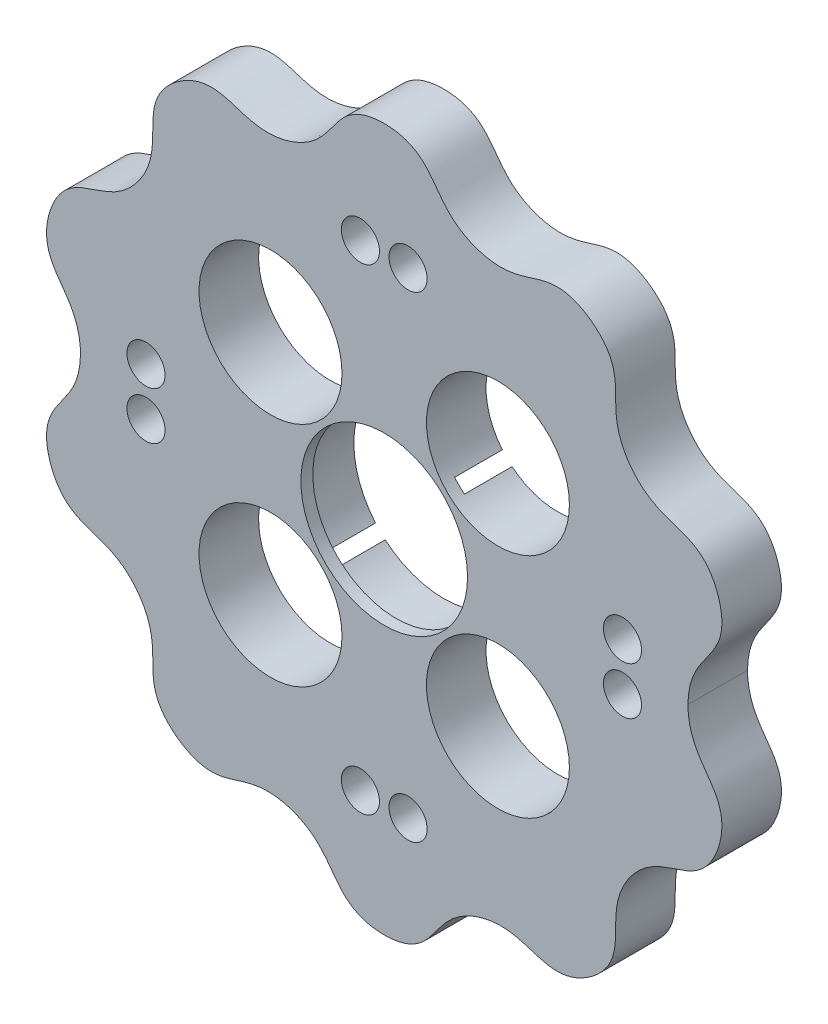
SolidWorks part; units mm, degrees
ref_plane "Front Plane" through (0, 0, 0) normal (0, 0, 1) x (1, 0, 0)
ref_plane "Top Plane" through (0, 0, 0) normal (0, 1, 0) x (1, 0, 0)
ref_plane "Right Plane" through (0, 0, 0) normal (1, 0, 0) x (0, 0, -1)
ref_plane "Plane1" through (0, 0, 4) normal (0, 0, 1) x (1, 0, 0)
sketch "Sketch3" plane through (0, 0, 4) normal (0, 0, 1) x (1, 0, 0)
  circle A0 centre (2, 0) radius 7.5
  spline S0 degree 5 poles (-23.5, 0) (-23.5, -0.6619) (-23.5985, -1.4561) (-23.8874, -2.4734) (-24.5265, -3.4803) (-25.3239, -4.5428) (-25.7599, -5.1922) (-26.203, -6.107) (-26.3992, -6.9747) (-26.3685, -8.1757) (-26.0322, -9.4106) (-25.4671, -10.5179) (-24.8895, -11.2256) (-23.9802, -11.9083) (-23.1576, -12.2723) (-21.7572, -12.687) (-20.1242, -13.2676) (-18.7699, -14.5833) (-17.7259, -16.1905) (-17.3933, -18.0022) (-17.4393, -19.3418) (-17.4288, -20.3924) (-17.2271, -21.518) (-16.8759, -22.3353) (-16.145, -23.2889) (-15.1471, -24.0902) (-14.0391, -24.6539) (-13.1558, -24.8869) (-12.0189, -24.9048) (-11.1394, -24.7158) (-9.7628, -24.2281) (-8.1004, -23.738) (-6.2314, -24.0063) (-4.442, -24.693) (-3.1081, -25.9632) (-2.3579, -27.074) (-1.7319, -27.9177) (-0.9071, -28.7098) (-0.1425, -29.1646) (1.0093, -29.5065) (2.2876, -29.5682) (3.5153, -29.373) (4.3668, -29.0423) (5.2971, -28.3885) (5.8976, -27.7187) (6.7246, -26.515) (7.7814, -25.1413) (9.4513, -24.2598) (11.3025, -23.7636) (13.1282, -24.0071) (14.3881, -24.4648) (15.3905, -24.7795) (16.5233, -24.9355) (17.4092, -24.854) (18.5419, -24.4536) (19.6124, -23.7522) (20.4909, -22.8726) (20.9855, -22.1045) (21.3538, -21.0288) (21.4458, -20.1339) (21.4074, -18.674) (21.455, -16.9415) (22.2878, -15.2469) (23.4937, -13.7573) (25.1139, -12.8812) (26.4022, -12.5109) (27.3981, -12.1763) (28.4063, -11.6367) (29.0751, -11.05) (29.7562, -10.0602) (30.2099, -8.8636) (30.4037, -7.6356) (30.3523, -6.7236) (30.018, -5.6368) (29.5664, -4.8587) (28.6772, -3.7002) (27.9235, -2.6005) (27.5985, -1.4561) (27.5, -0.6619) (27.5, 0) knots 0.5 0.5 0.5 0.5 0.5 0.5 0.516667 0.52 0.526667 0.53 0.533333 0.536667 0.546667 0.55 0.56 0.563333 0.566667 0.57 0.58 0.583333 0.6 0.61 0.616667 0.626667 0.63 0.633333 0.636667 0.646667 0.65 0.66 0.663333 0.666667 0.67 0.68 0.683333 0.7 0.71 0.716667 0.726667 0.73 0.733333 0.736667 0.746667 0.75 0.76 0.763333 0.766667 0.77 0.78 0.783333 0.8 0.81 0.816667 0.826667 0.83 0.833333 0.836667 0.846667 0.85 0.86 0.863333 0.866667 0.87 0.88 0.883333 0.9 0.91 0.916667 0.926667 0.93 0.933333 0.936667 0.946667 0.95 0.96 0.963333 0.966667 0.97 0.98 0.983333 1 1 1 1 1 1 weights 1 1 1 1 1 1 1 1 1 1 1 1 1 1 1 1 1 1 1 1 1 1 1 1 1 1 1 1 1 1 1 1 1 1 1 1 1 1 1 1 1 1 1 1 1 1 1 1 1 1 1 1 1 1 1 1 1 1 1 1 1 1 1 1 1 1 1 1 1 1 1 1 1 1 1 1 1 1 1 1
  spline S1 degree 5 poles (27.5, 0) (27.5, 0.6619) (27.5985, 1.4561) (27.8874, 2.4734) (28.5265, 3.4803) (29.3239, 4.5428) (29.7599, 5.1922) (30.203, 6.107) (30.3992, 6.9747) (30.3685, 8.1757) (30.0322, 9.4106) (29.4671, 10.5179) (28.8895, 11.2256) (27.9802, 11.9083) (27.1576, 12.2723) (25.7572, 12.687) (24.1242, 13.2676) (22.7699, 14.5833) (21.7259, 16.1905) (21.3933, 18.0022) (21.4393, 19.3418) (21.4288, 20.3924) (21.2271, 21.518) (20.8759, 22.3353) (20.145, 23.2889) (19.1471, 24.0902) (18.0391, 24.6539) (17.1558, 24.8869) (16.0189, 24.9048) (15.1394, 24.7158) (13.7628, 24.2281) (12.1004, 23.738) (10.2314, 24.0063) (8.442, 24.693) (7.1081, 25.9632) (6.3579, 27.074) (5.7319, 27.9177) (4.9071, 28.7098) (4.1425, 29.1646) (2.9907, 29.5065) (1.7124, 29.5682) (0.4847, 29.373) (-0.3668, 29.0423) (-1.2971, 28.3885) (-1.8976, 27.7187) (-2.7246, 26.515) (-3.7814, 25.1413) (-5.4513, 24.2598) (-7.3025, 23.7636) (-9.1282, 24.0071) (-10.3881, 24.4648) (-11.3905, 24.7795) (-12.5233, 24.9355) (-13.4092, 24.854) (-14.5419, 24.4536) (-15.6124, 23.7522) (-16.4909, 22.8726) (-16.9855, 22.1045) (-17.3538, 21.0288) (-17.4458, 20.1339) (-17.4074, 18.674) (-17.455, 16.9415) (-18.2878, 15.2469) (-19.4937, 13.7573) (-21.1139, 12.8812) (-22.4022, 12.5109) (-23.3981, 12.1763) (-24.4063, 11.6367) (-25.0751, 11.05) (-25.7562, 10.0602) (-26.2099, 8.8636) (-26.4037, 7.6356) (-26.3523, 6.7236) (-26.018, 5.6368) (-25.5664, 4.8587) (-24.6772, 3.7002) (-23.9235, 2.6005) (-23.5985, 1.4561) (-23.5, 0.6619) (-23.5, 0) knots 0 0 0 0 0 0 0.016667 0.02 0.026667 0.03 0.033333 0.036667 0.046667 0.05 0.06 0.063333 0.066667 0.07 0.08 0.083333 0.1 0.11 0.116667 0.126667 0.13 0.133333 0.136667 0.146667 0.15 0.16 0.163333 0.166667 0.17 0.18 0.183333 0.2 0.21 0.216667 0.226667 0.23 0.233333 0.236667 0.246667 0.25 0.26 0.263333 0.266667 0.27 0.28 0.283333 0.3 0.31 0.316667 0.326667 0.33 0.333333 0.336667 0.346667 0.35 0.36 0.363333 0.366667 0.37 0.38 0.383333 0.4 0.41 0.416667 0.426667 0.43 0.433333 0.436667 0.446667 0.45 0.46 0.463333 0.466667 0.47 0.48 0.483333 0.5 0.5 0.5 0.5 0.5 0.5 weights 1 1 1 1 1 1 1 1 1 1 1 1 1 1 1 1 1 1 1 1 1 1 1 1 1 1 1 1 1 1 1 1 1 1 1 1 1 1 1 1 1 1 1 1 1 1 1 1 1 1 1 1 1 1 1 1 1 1 1 1 1 1 1 1 1 1 1 1 1 1 1 1 1 1 1 1 1 1 1 1
extrude "CYC Disk" add sketch "Sketch3" along normal blind 5
sketch "Sketch6" plane through (0, 0, 9) normal (0, 0, 1) x (1, 0, 0)
  line L0 (0, 0) -> (2, 0) construction
  circle A1 centre (2, 0) radius 7.55
  dimension "D2" = 15.1
  dimension "D1" = 2
extrude "Cam Bearing" cut sketch "Sketch6" against normal through all
sketch "Sketch8" plane through (0, 0, 9) normal (0, 0, 1) x (1, 0, 0)
  circle A0 centre (2, 0) radius 6.9953
  circle A1 centre (2, 0) radius 7.575
extrude "Cam Bearing Retainer" add sketch "Sketch8" against normal blind 1
sketch "Sketch9" plane through (0, 0, 9) normal (0, 0, 1) x (1, 0, 0)
  line L0 (2, 0) -> (2, 20) construction
  line L2 (4, 20) -> (2, 20)
  line L3 (2, 20) -> (0, 20)
  circle A2 centre (0, 20) radius 1.6
  circle A3 centre (4, 20) radius 1.6
  circle A4 centre (22, -2) radius 1.6
  circle A5 centre (22, 2) radius 1.6
  circle A6 centre (0, -20) radius 1.6
  circle A7 centre (4, -20) radius 1.6
  circle A8 centre (-18, 2) radius 1.6
  circle A9 centre (-18, -2) radius 1.6
  point P23 (2, 0)
  dimension "D3" = 2
  dimension "D4" = 3.2
  dimension "D5" = 3.2
  dimension "D6" = 4
  dimension "D1" = 2
  dimension "D2" = 20
extrude "Positioning Holes" cut sketch "Sketch9" against normal through all contours A3 | A5 | A4 | A7 | A6 | A9 | A8 | A2 region at (4, 21.5547, 9) region at (22, -2, 9) region at (22, 2, 9) region at (0, -20, 9) region at (4, -20, 9) region at (-18, 2, 9) region at (-18, -2, 9)
sketch "CYC Ouput Sketch" plane through (2, 0, 4) normal (0, 0, 1) x (1, 0, 0)
  line L1 (9.5459, 9.5459) -> (-9.5459, 9.5459) construction
  line L2 (-9.5459, 9.5459) -> (-9.5459, -9.5459) construction
  line L3 (-9.5459, -9.5459) -> (9.5459, -9.5459) construction
  line L4 (9.5459, -9.5459) -> (9.5459, 9.5459) construction
  circle A0 centre (0, 0) radius 13.5 construction
sketch "Sketch11" plane through (0, 0, 9) normal (0, 0, 1) x (1, 0, 0)
  circle A0 centre (11.5459, 9.5459) radius 6
  circle A1 centre (11.5459, -9.5459) radius 6
  circle A2 centre (-7.5459, -9.5459) radius 6
  circle A3 centre (-7.5459, 9.5459) radius 6
  dimension "D1" = 12
extrude "Output Holes" cut sketch "Sketch11" against normal through all
equation "\"CamBearingOut\"=15.1"
equation "\"D2@Sketch6\"=\"CamBearingOut\""
equation "\"RingPinShaft\"= 5.05"
equation "\"CenterBearingOut\"=32.05"
equation "\"RingPostIn\"=5.15"
